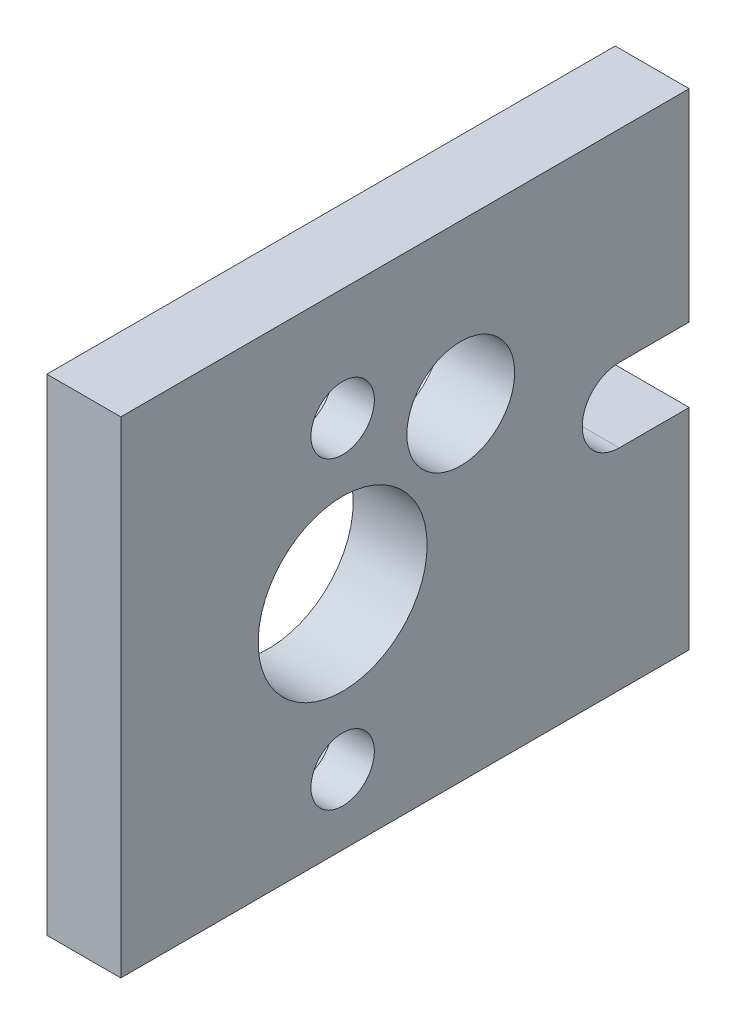
SolidWorks part; units mm, degrees
ref_plane "前视基准面" through (0, 0, 0) normal (0, 0, 1) x (1, 0, 0)
ref_plane "上视基准面" through (0, 0, 0) normal (0, 1, 0) x (1, 0, 0)
ref_plane "右视基准面" through (0, 0, 0) normal (1, 0, 0) x (0, 0, -1)
other "Configuration Table"
sketch "草图1" plane through (0, 0, 0) normal (1, 0, 0) x (0, 0, -1)
  line L6 (10.5, -10.5) -> (-10.5, -10.5)
  line L7 (10.5, -10.5) -> (10.5, 10.5)
  line L8 (10.5, 10.5) -> (-10.5, 10.5)
  line L9 (-10.5, -10.5) -> (-10.5, 10.5)
  line L10 (10.5, -10.5) -> (-10.5, 10.5) construction
  line L11 (10.5, 10.5) -> (-10.5, -10.5) construction
  circle A0 centre (0, 0) radius 4
  point P0 (0, 0)
  dimension "D1" = 21
  dimension "D3" = 8
extrude "凸台-拉伸1" add sketch "草图1" along normal blind 3.5 contours A0 L8 region at (0, -10.203, 0)
sketch "草图2" plane through (0, 0, 0) normal (-1, 0, 0) x (0, 0, 1)
  line L0 (0, 7.2) -> (0, -7.2) construction
  circle A0 centre (0, 7.2) radius 2.25
  circle A1 centre (0, -7.2) radius 2.25
  circle A2 centre (0, 7.2) radius 1.5
  circle A3 centre (0, -7.2) radius 1.5
  dimension "D2" = 3
  dimension "D3" = 4.5
  dimension "D1" = 14.4
extrude "切除-拉伸1" cut sketch "草图2" against normal offset from surface (1.5 mm away) 2 up to face at (3.5, 0, -4)
extrude "切除-拉伸2" cut sketch "草图2<2>" against normal through all contours A3 | A2 region at (0, 7.2, 0) region at (0, -7.2, 0)
sketch "草图2<2>" plane through (0, 0, 0) normal (-1, 0, 0) x (0, 0, 1) same geometry as "草图2"
sketch "草图4" plane through (0, 0, 0) normal (-1, 0, 0) x (0, 0, 1)
  circle A0 centre (-5.5902, 5) radius 2.55
  dimension "D3" = 5.1
  dimension "D1" = 7.5
  dimension "D2" = 5
extrude "切除-拉伸3" cut sketch "草图4" against normal through all
sketch "草图5" plane through (0, 0, 0) normal (-1, 0, 0) x (0, 0, 1)
  line L0 (-10.5, -10.5) -> (-10.5, 10.5) construction
  line L1 (-10.5, 10.5) -> (-16.4, 10.5)
  line L2 (-10.5, 10.5) -> (-10.5, -10.5)
  line L3 (-10.5, -10.5) -> (-16.4, -10.5)
  line L4 (-16.4, 10.5) -> (-16.4, -10.5)
  line L5 (-10.5, -10.5) -> (10.5, -10.5) construction
  line L6 (-10.5, 10.5) -> (10.5, 10.5) construction
  line L7 (-16.4, 2.9343) -> (-13.0902, 2.9343)
  line L8 (-16.4, -0.5657) -> (-13.0902, -0.5657)
  circle A0 centre (-13.0902, 1.1843) radius 1.75
  line M11 (-10.5, 10.5) -> (-10.5, -10.5)
  dimension "D2" = 3.5
  dimension "D1" = 5.9
extrude "凸台-拉伸2" add sketch "草图5" against normal up to surface (3.5 mm away) contours A0 L8 L4 L3 L1 L7 M11 region at (0, 0, -10.7181) up to face at (3.5, 5, -3.0402)
sketch "草图6" plane through (0, 0, 0) normal (-1, 0, 0) x (0, 0, 1)
  line L0 (-16.4, 10.5) -> (-16.4, 2.9343) construction
  line L1 (-16.4, 10.5) -> (10.5, 10.5)
  line L2 (-16.4, 10.5) -> (-16.4, 12.5)
  line L3 (-16.4, 12.5) -> (10.5, 12.5)
  line L4 (10.5, 10.5) -> (10.5, 12.5)
  line L5 (10.5, -10.5) -> (10.5, 10.5) construction
  dimension "D1" = 2
extrude "凸台-拉伸3" add sketch "草图6" against normal up to surface (3.5 mm away) up to face at (3.5, 5, -3.0402)
